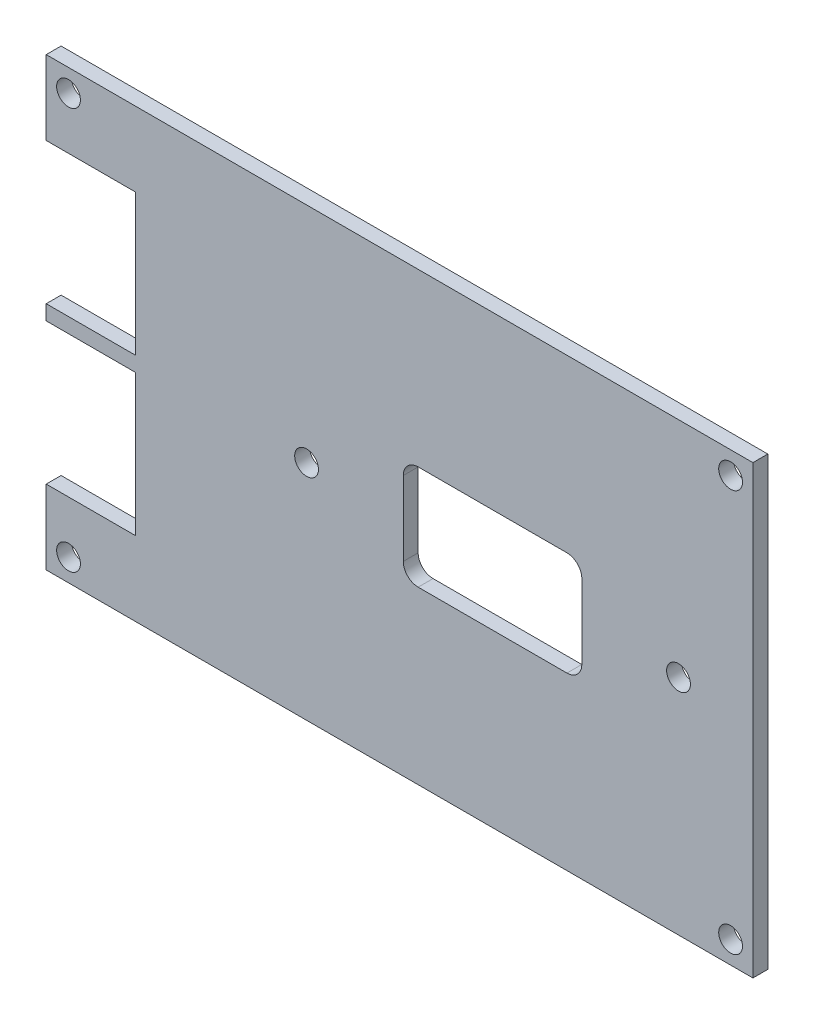
SolidWorks part; units mm, degrees
ref_plane "Front Plane" through (0, 0, 0) normal (0, 0, 1) x (1, 0, 0)
ref_plane "Top Plane" through (0, 0, 0) normal (0, 1, 0) x (1, 0, 0)
ref_plane "Right Plane" through (0, 0, 0) normal (1, 0, 0) x (0, 0, -1)
sketch "Sketch1" plane through (0, 0, 0) normal (0, 0, 1) x (1, 0, 0)
  line L0 (-4.5636, -11.1185) -> (20.4364, -11.1185) construction
  line L1 (-39.5636, 18.8815) -> (55.4364, 18.8815)
  line L2 (-39.5636, 18.8815) -> (-39.5636, 8.8815)
  line L3 (-39.5636, -41.1185) -> (55.4364, -41.1185)
  line L4 (55.4364, 18.8815) -> (55.4364, -41.1185)
  line L5 (20.4364, -4.1185) -> (20.4364, -11.1185) construction
  line L6 (10.4364, -4.1185) -> (30.4364, -4.1185)
  line L7 (8.4364, -6.1185) -> (8.4364, -16.1185)
  line L8 (10.4364, -18.1185) -> (30.4364, -18.1185)
  line L9 (32.4364, -6.1185) -> (32.4364, -16.1185)
  line L10 (20.4364, -18.1185) -> (20.4364, -11.1185) construction
  line L11 (20.4364, -11.1185) -> (45.4364, -11.1185) construction
  line L12 (-39.5636, -10.1185) -> (-39.5636, -12.1185)
  line L13 (-39.5636, 8.8815) -> (-27.5636, 8.8815)
  line L15 (-39.5636, -10.1185) -> (-27.5636, -10.1185)
  line L16 (-27.5636, 8.8815) -> (-27.5636, -10.1185)
  line L17 (-39.5636, -31.1185) -> (-39.5636, -41.1185)
  line L18 (-39.5636, -12.1185) -> (-27.5636, -12.1185)
  line L20 (-39.5636, -31.1185) -> (-27.5636, -31.1185)
  line L21 (-27.5636, -12.1185) -> (-27.5636, -31.1185)
  line L22 (-27.5636, 8.8815) -> (-27.5636, 18.8815) construction
  line L23 (-27.5636, -31.1185) -> (-27.5636, -41.1185) construction
  circle A0 centre (45.4364, -11.1185) radius 1.6
  circle A1 centre (-4.5636, -11.1185) radius 1.6
  circle A2 centre (-36.5636, 15.8815) radius 1.6
  circle A3 centre (52.4364, 15.8815) radius 1.6
  circle A4 centre (-36.5636, -38.1185) radius 1.6
  circle A5 centre (52.4364, -38.1185) radius 1.6
  arc A6 (10.4364, -4.1185) -> (8.4364, -6.1185) centre (10.4364, -6.1185) ccw
  arc A7 (32.4364, -6.1185) -> (30.4364, -4.1185) centre (30.4364, -6.1185) ccw
  arc A8 (10.4364, -18.1185) -> (8.4364, -16.1185) centre (10.4364, -16.1185) cw
  arc A9 (30.4364, -18.1185) -> (32.4364, -16.1185) centre (30.4364, -16.1185) ccw
  dimension "D3" = 50
  dimension "D6" = 2
  dimension "D7" = 2
  dimension "D8" = 2
  dimension "D9" = 2
  dimension "D1" = 60
  dimension "D2" = 95
  dimension "D4" = 10
  dimension "D5" = 30
  dimension "D10" = 20
  dimension "D11" = 10
  dimension "D12" = 3
  dimension "D13" = 3
  dimension "D14" = 3
  dimension "D15" = 3
  dimension "D16" = 3
  dimension "D17" = 3
  dimension "D18" = 3
  dimension "D19" = 3
  dimension "D20" = 54
  dimension "D21" = 12
  dimension "D22" = 19
  dimension "D23" = 10
extrude "Boss-Extrude1" add sketch "Sketch1" along normal blind 2
